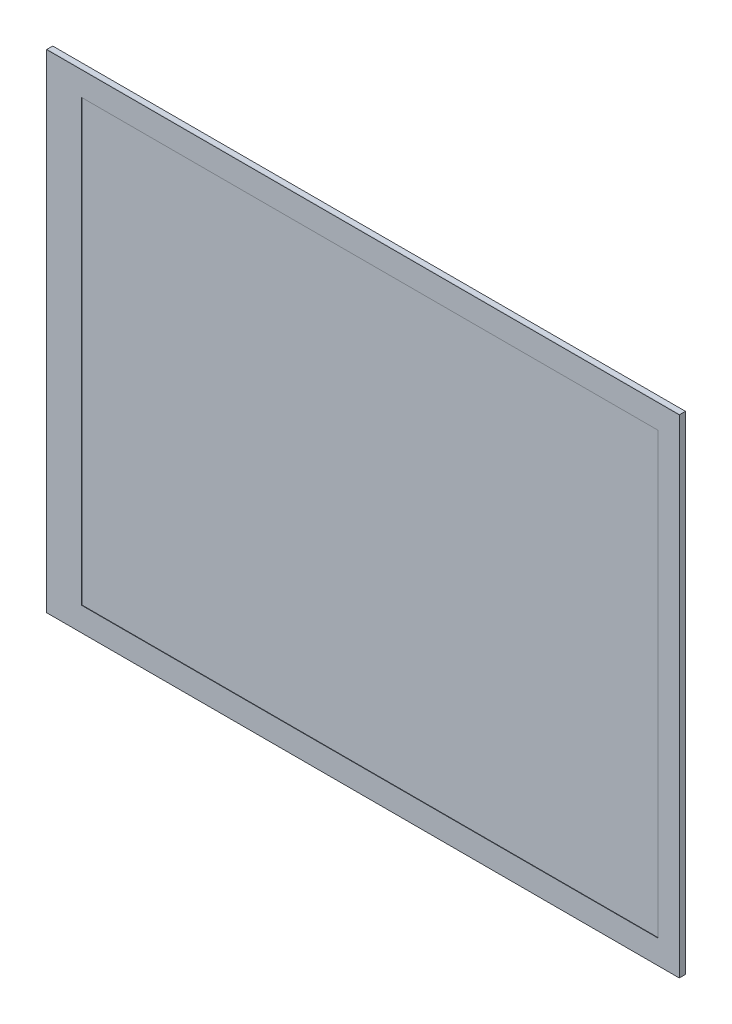
SolidWorks part; units mm, degrees
ref_plane "Front Plane" through (0, 0, 0) normal (0, 0, 1) x (1, 0, 0)
ref_plane "Top Plane" through (0, 0, 0) normal (0, 1, 0) x (1, 0, 0)
ref_plane "Right Plane" through (0, 0, 0) normal (1, 0, 0) x (0, 0, -1)
sketch "Sketch1" plane through (0, 0, 0) normal (0, 0, 1) x (1, 0, 0)
  line L1 (0, 0) -> (144, 0)
  line L2 (0, 0) -> (0, 111)
  line L3 (0, 111) -> (144, 111)
  line L4 (144, 0) -> (144, 111)
  dimension "D1" = 144
  dimension "D2" = 111
extrude "Boss-Extrude1" add sketch "Sketch1" along normal blind 1.3
sketch "Sketch2" plane through (0, 0, 1.3) normal (0, 0, 1) x (1, 0, 0)
  line L0 (0, 111) -> (0, 0) construction
  line L1 (0, 66.5) -> (-3, 66.5)
  line L2 (0, 66.5) -> (0, 44.5)
  line L3 (0, 44.5) -> (-3, 44.5)
  line L4 (-4, 65.5) -> (-4, 59)
  line L5 (0, 66.5) -> (0, 111) construction
  line L6 (0, 44.5) -> (0, 0) construction
  line L7 (-5, 58) -> (-10, 58)
  line L8 (-10, 58) -> (-10, 53)
  line L9 (-10, 53) -> (-5, 53)
  line L10 (-4, 52) -> (-4, 45.5)
  line L11 (-10, 55.5) -> (0, 55.5) construction
  line L12 (144, 111) -> (0, 111) construction
  arc A0 (-3, 44.5) -> (-4, 45.5) centre (-3, 45.5) cw
  arc A1 (-4, 65.5) -> (-3, 66.5) centre (-3, 65.5) cw
  arc A2 (-4, 52) -> (-5, 53) centre (-5, 52) ccw
  arc A3 (-5, 58) -> (-4, 59) centre (-5, 59) ccw
  point P12 (-4, 44.5)
  point P15 (-4, 66.5)
  dimension "D3" = 1
  dimension "D5" = 1
  dimension "D1" = 22
  dimension "D2" = 4
  dimension "D4" = 5
  dimension "D6" = 10
  dimension "D7" = 55.5
extrude "Boss-Extrude2" add sketch "Sketch2" against normal blind 0.1
sketch "Sketch5" plane through (0, 0, 1.3) normal (0, 0, 1) x (1, 0, 0)
  line L0 (144, 111) -> (0, 111) construction
  line L1 (144, 111) -> (0, 111)
  line L2 (144, 0) -> (144, 111) construction
  line L3 (0, 0) -> (144, 0) construction
  line L4 (0, 44.5) -> (0, 0) construction
  line L5 (0, 44.5) -> (0, 66.5) construction
  line L6 (0, 111) -> (0, 66.5) construction
  line L7 (144, 0) -> (144, 111)
  line L8 (0, 0) -> (144, 0)
  line L9 (0, 44.5) -> (0, 0)
  line L10 (0, 44.5) -> (0, 66.5)
  line L11 (0, 111) -> (0, 66.5)
  line L12 (139.2, 105.55) -> (8, 105.55)
  line L13 (8, 105.55) -> (8, 5.45)
  line L16 (8, 5.45) -> (139.2, 5.45)
  line L17 (139.2, 5.45) -> (139.2, 105.55)
  dimension "D1" = 5.45
  dimension "D2" = 4.8
  dimension "D3" = 5.45
  dimension "D4" = 8
extrude "Boss-Extrude3" add sketch "Sketch5" along normal blind 0.1 separate body
split "Split1" bodies to split 102 resulting bodies 105 106 split by face at (0, 61.0625, 0.9375)
move or copy body "Body-Move/Copy1" bodies to move or copy 105 copy no rotation origin (0, 0, 1.4) rotation axis (0, -1, 0) rotation angle 90
